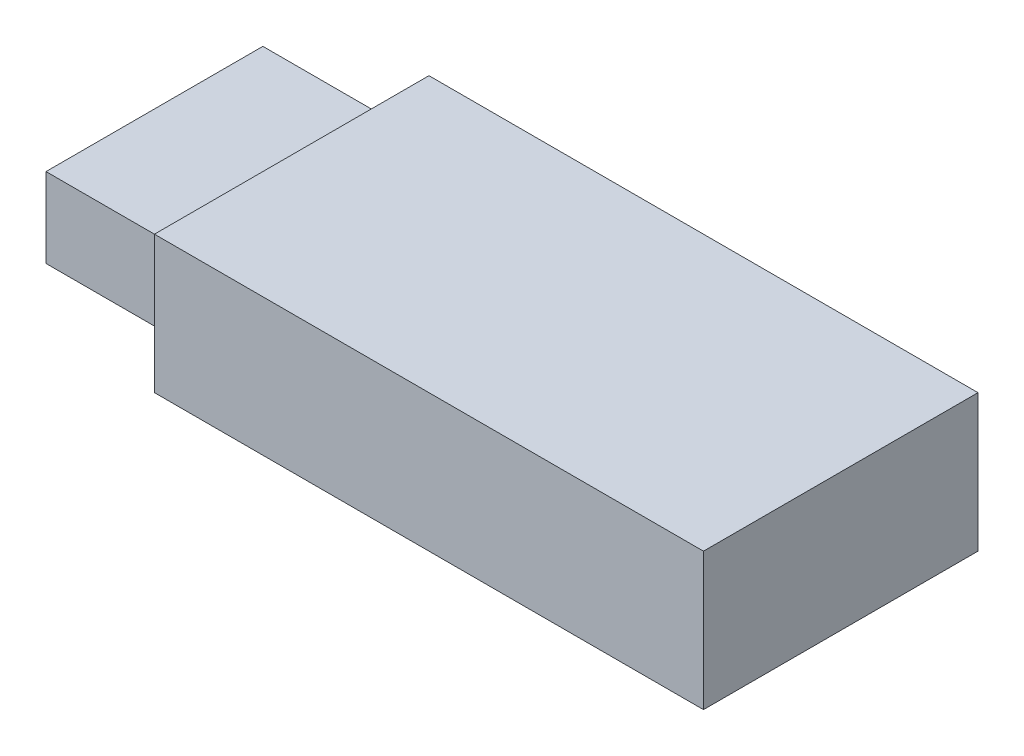
SolidWorks part; units mm, degrees
ref_plane "前视基准面" through (0, 0, 0) normal (0, 0, 1) x (1, 0, 0)
ref_plane "上视基准面" through (0, 0, 0) normal (0, 1, 0) x (1, 0, 0)
ref_plane "右视基准面" through (0, 0, 0) normal (1, 0, 0) x (0, 0, -1)
sketch "草图1" plane through (0, 0, 0) normal (0, 1, 0) x (1, 0, 0)
  line L1 (0, 0) -> (100, 0)
  line L2 (0, 0) -> (0, 40)
  line L3 (0, 40) -> (100, 40)
  line L4 (100, 0) -> (100, 40)
  dimension "D1" = 100
  dimension "D2" = 40
extrude "凸台-拉伸1" add sketch "草图1" along normal blind 20 contours L2 L3 L4 L1
sketch "草图3" plane through (0, 0, 0) normal (-1, 0, 0) x (0, 0, 1)
  line L3 (-40, 10) -> (0, 10)
  line L6 (-20, 16) -> (-20, 4)
  line L7 (-36, 16) -> (-4, 16)
  line L8 (-36, 16) -> (-36, 4)
  line L9 (-36, 4) -> (-4, 4)
  line L10 (-4, 16) -> (-4, 4)
  line L11 (-40, 20) -> (-40, 0) construction
  line L12 (0, 20) -> (0, 0) construction
  point P3 (-20, 10)
  line M5 (-40, 0) -> (0, 0)
  line M6 (0, 0) -> (0, 20)
  line M7 (0, 20) -> (-40, 20)
  line M8 (-40, 20) -> (-40, 0)
  dimension "D1" = 32
  dimension "D2" = 16
  dimension "D3" = 12
  dimension "D4" = 6
sketch "草图5" plane through (0, 0, 0) normal (-1, 0, 0) x (0, 0, 1)
extrude "切除-拉伸4" cut sketch "草图3" against normal blind 20 contours L7 L10 L3 L8 M6 M7 M8 | L3 L10 L9 L8 M8 M5 M6 region at (0, 16.8462, -20) region at (0, 3.1538, -20)
sketch "草图6" plane through (0, 0, 0) normal (-1, 0, 0) x (0, 0, 1)
  line L0 (-36, 10) -> (-4, 10) construction
  line L1 (-36, 16) -> (-36, 4) construction
  line L2 (-4, 16) -> (-4, 4) construction
  line L3 (-36, 16) -> (-4, 16) construction
  line L4 (-35.8, 15.8) -> (-4.2, 15.8)
  line L5 (-35.8, 15.8) -> (-35.8, 4.2)
  line L6 (-35.8, 4.2) -> (-4.2, 4.2)
  line L7 (-4.2, 15.8) -> (-4.2, 4.2)
  line L8 (-4, 16) -> (-4, 4) construction
  line L9 (-36, 4) -> (-4, 4) construction
  line L10 (-36, 16) -> (-36, 4) construction
  line M5 (-4, 16) -> (-36, 16)
  line M6 (-36, 16) -> (-36, 4)
  line M7 (-36, 4) -> (-4, 4)
  line M8 (-4, 4) -> (-4, 16)
  dimension "D1" = 0.2
  dimension "D2" = 0.2
  dimension "D3" = 0.2
  dimension "D4" = 0.2
extrude "切除-拉伸5" cut sketch "草图6" against normal blind 20 contours L0 L5 L4 L7 M6 M8 M5 | L0 L7 L6 L5 M6 M7 M8 region at (0, 13, -35.9674) region at (0, 9.6744, -35.9)
ref_point "点1"
ref_point "点2"
ref_axis "基准轴5" through (0, 10, -20) along (1, 0, 0)
ref_axis "基准轴6" through (100, 0, -20) along (-1, 0, 0)
